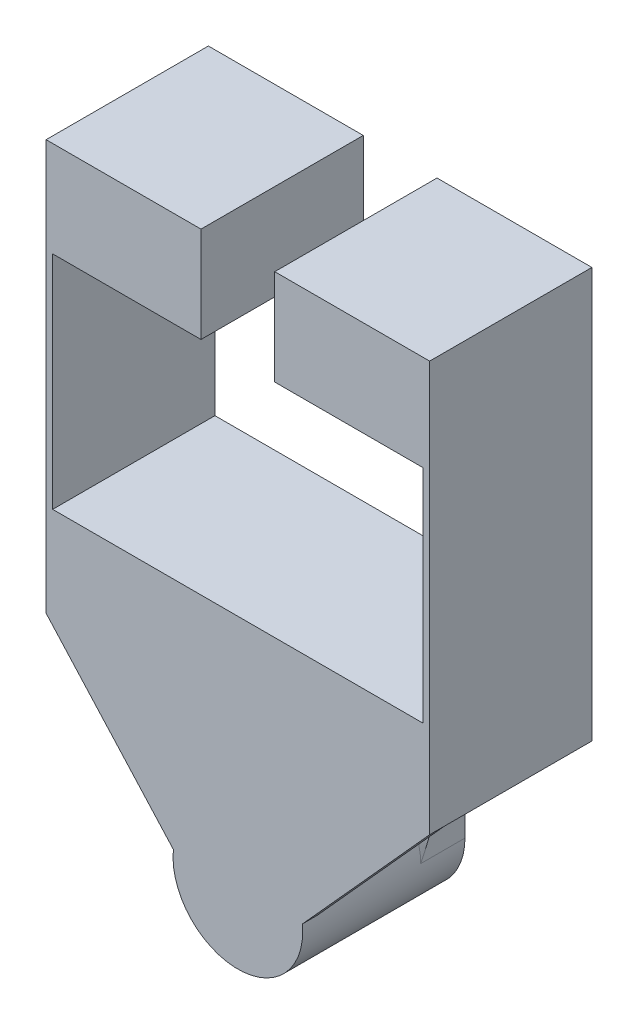
SolidWorks part; units mm, degrees
other "Markup1"
sketch "Sketch7" plane through (31.7043, 97.4003, 0) normal (0.5774, 0.5773, 0.5774) x (0.7071, 0, -0.7071)
material "ASTM A36 Steel"
ref_plane "Front Plane" through (0, 0, 0) normal (0, 0, 1) x (1, 0, 0)
ref_plane "Top Plane" through (0, 0, 0) normal (0, 1, 0) x (1, 0, 0)
ref_plane "Right Plane" through (0, 0, 0) normal (1, 0, 0) x (0, 0, -1)
sketch "Sketch1" plane through (0, 0, 0) normal (0, 0, 1) x (1, 0, 0)
  circle A0 centre (0, 0) radius 11.1628
  dimension "D1" = 22.3256
extrude "Boss-Extrude1" add sketch "Sketch1" against normal blind 25.4
sketch "Sketch2" plane through (0, 0, -25.4) normal (0, 0, -1) x (-1, 0, 0)
  line L0 (-11.1628, 0) -> (-11.1628, 25.4)
  line L1 (-11.1628, 25.4) -> (11.1628, 25.4)
  line L2 (11.1628, 25.4) -> (11.1628, 0)
  circle A0 centre (0, 0) radius 11.1628 construction
  arc A1 (11.1628, 0) -> (-11.1628, 0) centre (0, 0) ccw
  dimension "D1" = 22.3256
extrude "Boss-Extrude2" add sketch "Sketch2" against normal blind 2.54
ref_plane "Plane1" through (0, 25.4, 0) normal (0, 1, 0) x (1, 0, 0)
sketch "Sketch4" plane through (0, 25.4, 0) normal (0, 1, 0) x (1, 0, 0)
  line L0 (0, 0) -> (0, 55.2267) construction
  line L1 (-33.02, 0) -> (33.02, 0)
  line L2 (-33.02, 0) -> (-33.02, 25.4)
  line L3 (-33.02, 25.4) -> (33.02, 25.4)
  line L4 (33.02, 0) -> (33.02, 25.4)
  point P6 (0, 0)
  dimension "D2" = 66.04
extrude "Boss-Extrude3" add sketch "Sketch4" along normal blind 16.0644
sketch "Sketch5" plane through (0, 41.4644, 0) normal (0, 1, 0) x (1, 0, 0)
  line L0 (-33.02, 0) -> (33.02, 0) construction
  line L1 (-33.02, 25.4) -> (-31.8904, 25.4)
  line L2 (-33.02, 25.4) -> (-33.02, 0)
  line L3 (-33.02, 0) -> (-31.8904, 0)
  line L4 (-31.8904, 25.4) -> (-31.8904, 0)
  line L6 (33.02, 25.4) -> (31.8904, 25.4)
  line L7 (33.02, 25.4) -> (33.02, 0)
  line L8 (33.02, 0) -> (31.8904, 0)
  line L9 (31.8904, 25.4) -> (31.8904, 0)
  dimension "D1" = 1.1296
  dimension "D2" = 1.1296
extrude "Boss-Extrude4" add sketch "Sketch5" along normal blind 38.1
sketch "Sketch6" plane through (0, 79.5644, 0) normal (0, 1, 0) x (1, 0, 0)
  line L0 (31.8904, 25.4) -> (-31.8904, 25.4) construction
  line L1 (33.02, 0) -> (6.35, 0)
  line L2 (33.02, 0) -> (33.02, 25.4)
  line L3 (33.02, 25.4) -> (6.35, 25.4)
  line L4 (6.35, 0) -> (6.35, 25.4)
  line L5 (0, 0) -> (0, 25.4) construction
  line L6 (-6.35, 0) -> (-6.35, 25.4)
  line L7 (-33.02, 25.4) -> (-6.35, 25.4)
  line L8 (-33.02, 0) -> (-33.02, 25.4)
  line L9 (-33.02, 0) -> (-6.35, 0)
  dimension "D1" = 26.67
extrude "Boss-Extrude5" add sketch "Sketch6" along normal blind 16.4611
sketch "Sketch10" plane through (0, 0, -25.4) normal (0, 0, -1) x (-1, 0, 0)
  line L15 (11.1628, 0) -> (11.1628, 25.4)
  line L16 (11.1628, 25.4) -> (33.02, 25.4)
  line L17 (33.02, 25.4) -> (33.02, 96.0255)
  line L18 (33.02, 96.0255) -> (6.35, 96.0255)
  line L19 (6.35, 96.0255) -> (6.35, 79.5644)
  line L20 (6.35, 79.5644) -> (31.8904, 79.5644)
  line L21 (31.8904, 79.5644) -> (31.8904, 41.4644)
  line L22 (31.8904, 41.4644) -> (-31.8904, 41.4644)
  line L23 (-31.8904, 41.4644) -> (-31.8904, 79.5644)
  line L24 (-31.8904, 79.5644) -> (-6.35, 79.5644)
  line L25 (-6.35, 79.5644) -> (-6.35, 96.0255)
  line L26 (-6.35, 96.0255) -> (-33.02, 96.0255)
  line L27 (-33.02, 96.0255) -> (-33.02, 25.4)
  line L28 (-33.02, 25.4) -> (-11.1628, 25.4)
  line L29 (-11.1628, 25.4) -> (-11.1628, 0)
  line L30 (11.1628, 0) -> (11.1628, 25.4)
  line L31 (11.1628, 25.4) -> (33.02, 25.4)
  line L32 (33.02, 25.4) -> (33.02, 96.0255)
  line L33 (33.02, 96.0255) -> (6.35, 96.0255)
  line L34 (6.35, 96.0255) -> (6.35, 79.5644)
  line L35 (6.35, 79.5644) -> (31.8904, 79.5644)
  line L36 (31.8904, 79.5644) -> (31.8904, 41.4644)
  line L37 (31.8904, 41.4644) -> (-31.8904, 41.4644)
  line L38 (-31.8904, 41.4644) -> (-31.8904, 79.5644)
  line L39 (-31.8904, 79.5644) -> (-6.35, 79.5644)
  line L40 (-6.35, 79.5644) -> (-6.35, 96.0255)
  line L41 (-6.35, 96.0255) -> (-33.02, 96.0255)
  line L42 (-33.02, 96.0255) -> (-33.02, 25.4)
  line L43 (-33.02, 25.4) -> (-11.1628, 25.4)
  line L44 (-11.1628, 25.4) -> (-11.1628, 0)
  arc A1 (-11.1628, 0) -> (11.1628, 0) centre (0, 0) ccw
  arc A2 (-11.1628, 0) -> (11.1628, 0) centre (0, 0) ccw
  dimension "D1" = 0
extrude "Boss-Extrude8" add sketch "Sketch10" along normal blind 2.54
sketch "Sketch11" plane through (33.02, 0, 0) normal (1, 0, 0) x (0, 0, -1)
  line L0 (13.97, 25.4) -> (22.86, 12.7)
  line L1 (0, 25.4) -> (27.94, 25.4) construction
  line L2 (22.86, 25.4) -> (22.86, 0) construction
  line L3 (22.86, 12.7) -> (22.86, 25.4)
  line L4 (22.86, 25.4) -> (13.97, 25.4)
extrude "Boss-Extrude9" add sketch "Sketch11" against normal through all
sketch "Sketch12" plane through (0, 0, -22.86) normal (0, 0, 1) x (1, 0, 0)
  line L0 (-11.1628, 12.7) -> (11.1628, 12.7)
  line L1 (11.1628, 12.7) -> (11.1628, 25.4)
  line L2 (-33.02, 25.4) -> (33.02, 25.4) construction
  line L3 (11.1628, 25.4) -> (-11.1628, 25.4)
  line L4 (-11.1628, 25.4) -> (-11.1628, 12.7)
  line L6 (11.1628, 12.7) -> (33.02, 12.7)
  line L7 (11.1628, 12.7) -> (11.1628, 25.4)
  line L8 (11.1628, 25.4) -> (33.02, 25.4)
  line L9 (33.02, 12.7) -> (33.02, 25.4)
  line L10 (-11.1628, 12.7) -> (-33.02, 12.7)
  line L11 (-11.1628, 12.7) -> (-11.1628, 25.4)
  line L12 (-11.1628, 25.4) -> (-33.02, 25.4)
  line L13 (-33.02, 12.7) -> (-33.02, 25.4)
extrude "Cut-Extrude3" cut sketch "Sketch12" along normal blind 30.734 contours L13 L10 L4 L12 | L6 L9 L8 L1 region at (-22.0914, 19.05, -22.86) region at (22.0914, 19.05, -22.86)
fillet "Fillet1" radius 2.54 2 edges at (0, 12.7, -22.86) (0, 11.1628, -22.86)
sketch "Sketch13" plane through (0, 0, 0) normal (0, 0, 1) x (1, 0, 0)
  line L0 (-33.02, 25.4) -> (-11.1051, 1.1338)
  line L1 (11.1051, 1.1338) -> (33.02, 25.4)
  line L2 (33.02, 25.4) -> (-33.02, 25.4)
  arc A1 (-11.1051, 1.1338) -> (11.1051, 1.1338) centre (0, 0) ccw
  dimension "D3" = 11.1628
  dimension "D1" = 7.4817
  dimension "D2" = 7.4817
extrude "Boss-Extrude10" add sketch "Sketch13" against normal blind 2.54
equation "\"F\"= 600"
equation "\"E\"= 29000000"
equation "\"Sy\"= 36000"
equation "\"Tallow\"= 9000"
equation "\"La\"= 1in"
equation "\"SF\"= 4"
equation "\"Z\"=  ( \"SF\" *  ( 2 * \"F\" )  * \"La\" )  /  ( 2 * \"Sy\" ) "
equation "\"Ra\"= ( ( \"Z\" / pi ) * 4 ) ^ ( 1 / 3 )"
equation "\"Bw\"= .879in"
equation "\"Ba\"= ( \"SF\" * \"F\" ) / ( \"Sy\" )"
equation "\"Tb\"= \"Ba\" / \"Bw\""
equation "\"Cw\"=2.6"
equation "\"Ct\"= 1"
equation "\"Ca\"= ( \"SF\" * ( 2 * \"F\" ) ) / \"Sy\""
equation "\"Ch\"= ( \"Z\" * 6 ) ^ ( 1 / 2 )"
equation "\"Da\"= ( \"F\" * \"SF\" ) / ( \"Sy\" )"
equation "\"Dh\"= 1.499"
equation "\"Dw\"= \"Da\" / \"Dh\""
equation "\"Ea\"= ( \"F\" * \"SF\" ) / ( \"Sy\" )"
equation "\"Ew\"=1.05"
equation "\"Ad\"= \"Ra\" * 2"
equation "\"D1@Sketch1\"=\"Ad\""
equation "\"D1@Boss-Extrude1\"=\"La\""
equation "\"D1@Boss-Extrude2\"=.1"
equation "\"D1@Sketch2\"=\"Ad\""
equation "\"D2@Sketch4\"=\"Cw\""
equation "\"D1@Boss-Extrude3\"=\"Ch\""
equation "\"D1@Sketch5\"=\"Dw\""
equation "\"D2@Sketch5\"=\"Dw\""
equation "\"D1@Sketch6\"=\"Ew\""
equation "\"D1@Boss-Extrude5\"=\"Eh\""
equation "\"Ehtop\"= ( 6 * \"F\" * \"Ew\" * \"SF\" )"
equation "\"Ehbottom\"= ( 1 * \"Sy\" )"
equation "\"Eh\"= ( \"Ehtop\" / \"Ehbottom\" ) ^ ( 1 / 2 )"
